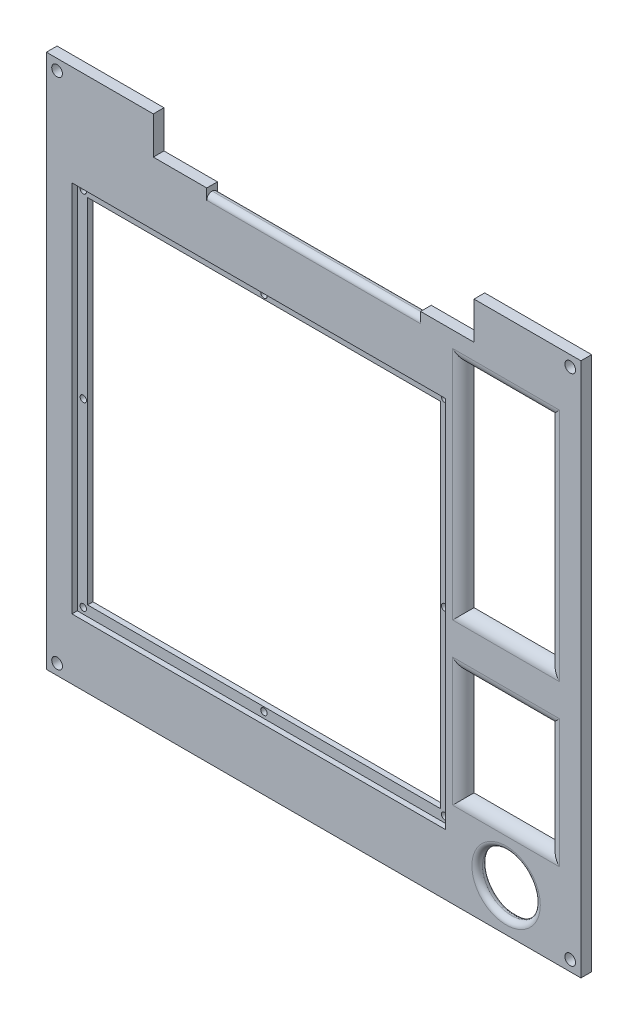
SolidWorks part; units mm, degrees
ref_plane "Ebene vorne" through (0, 0, 0) normal (0, 0, 1) x (1, 0, 0)
ref_plane "Ebene oben" through (0, 0, 0) normal (0, 1, 0) x (1, 0, 0)
ref_plane "Ebene rechts" through (0, 0, 0) normal (1, 0, 0) x (0, 0, -1)
sketch "Sketch1" plane through (0, 0, 0) normal (0, 0, 1) x (1, 0, 0)
  line L1 (0, 0) -> (-250, 0)
  line L2 (0, 0) -> (0, 250)
  line L3 (0, 250) -> (-250, 250)
  line L4 (-250, 0) -> (-250, 250)
  dimension "D1" = 250
  dimension "D2" = 250
extrude "Boss-Extrude1" add sketch "Sketch1" along normal blind 50
sketch "Sketch2" plane through (0, 0, 50) normal (0, 0, 1) x (1, 0, 0)
  line L0 (-125, 250) -> (-125, 0) construction
  line L1 (0, 250) -> (-250, 250) construction
  line L2 (-250, 0) -> (0, 0) construction
  line L5 (0, 0) -> (0, 250) construction
  line L7 (-55, 220) -> (-15, 220)
  line L8 (-55, 220) -> (-55, 120)
  line L9 (-55, 120) -> (-15, 120)
  line L10 (-15, 220) -> (-15, 120)
  line L14 (-55, 95) -> (-15, 95)
  line L15 (-55, 95) -> (-55, 45)
  line L16 (-55, 45) -> (-15, 45)
  line L17 (-15, 95) -> (-15, 45)
  dimension "D1" = 100
  dimension "D2" = 40
  dimension "D3" = 30
  dimension "D4" = 15
  dimension "D5" = 50
  dimension "D6" = 25
extrude "Cut-Extrude1" cut sketch "Sketch2" against normal blind 45
fillet "Fillet1" radius 5 4 edges at (-35, 120, 50) (-15, 170, 50) (-55, 170, 50) (-35, 220, 50)
fillet "Fillet2" radius 5 4 edges at (-35, 45, 50) (-15, 70, 50) (-35, 95, 50) (-55, 70, 50)
sketch "Sketch4" plane through (0, 0, 50) normal (0, 0, 1) x (1, 0, 0)
  line L0 (0, 250) -> (-250, 250) construction
  line L1 (-200, 250) -> (-175, 250)
  line L2 (-200, 250) -> (-200, 232.5)
  line L3 (-200, 232.5) -> (-175, 232.5)
  line L4 (-175, 250) -> (-175, 232.5)
  line L5 (-125, 250) -> (-125, 0) construction
  line L10 (-250, 0) -> (0, 0) construction
  line L11 (-50, 232.5) -> (-75, 232.5)
  line L12 (-75, 250) -> (-75, 232.5)
  line L13 (-50, 250) -> (-75, 250)
  line L14 (-50, 250) -> (-50, 232.5)
  dimension "D1" = 50
  dimension "D2" = 25
  dimension "D3" = 17.5
sketch "Sketch5" plane through (0, 0, 50) normal (0, 0, 1) x (1, 0, 0)
  line L0 (-235, 200) -> (-75, 200) construction
  line L1 (0, 250) -> (-250, 250) construction
  line L2 (-75, 200) -> (-75, 10) construction
  line L3 (-75, 10) -> (-235, 10) construction
  line L4 (-235, 10) -> (-235, 200) construction
  line L5 (-250, 250) -> (-250, 0) construction
  line L6 (-60, 115) -> (-60, 225) construction
  line L7 (-250, 0) -> (0, 0) construction
  line L9 (-235, 200) -> (-215, 200) construction
  line L10 (-235, 200) -> (-235, 180) construction
  line L11 (-235, 180) -> (-215, 180) construction
  line L12 (-215, 200) -> (-215, 180) construction
  line L13 (-235, 200) -> (-215, 180) construction
  line L14 (-235, 180) -> (-215, 200) construction
  circle A0 centre (-225, 190) radius 6.25
  dimension "D5" = 12.5
  dimension "D1" = 15
  dimension "D2" = 50
  dimension "D3" = 15
  dimension "D4" = 10
  dimension "D6" = 20
  dimension "D7" = 20
extrude "Cut-Extrude2" cut sketch "Sketch5" against normal blind 22
fillet "Fillet5" radius 1.5 1 edges at (-218.75, 190, 50)
pattern_linear "LPattern4" count 10 spacing 16.5 along (1, 0, 0) count 10 spacing 16.5 along (0, -1, 0) of "Cut-Extrude2", "Fillet5"
sketch "Sketch7" plane through (0, 0, 0) normal (0, 0, -1) x (-1, 0, 0)
  line L0 (250, 250) -> (250, 0) construction
  line L1 (5, 245) -> (245, 245)
  line L2 (5, 245) -> (5, 225)
  line L3 (5, 5) -> (245, 5)
  line L4 (245, 245) -> (245, 5)
  line L5 (0, 250) -> (250, 250) construction
  line L6 (0, 0) -> (0, 250) construction
  line L7 (250, 0) -> (0, 0) construction
  line L8 (5, 115) -> (5, 100)
  line L9 (5, 225) -> (60, 225)
  line L11 (5, 115) -> (60, 115)
  line L12 (60, 225) -> (60, 115)
  line L13 (5, 40) -> (60, 40)
  line L15 (5, 100) -> (60, 100)
  line L16 (60, 40) -> (60, 100)
  line L17 (5, 40) -> (5, 5)
  line L18 (60, 225) -> (10, 225) construction
  dimension "D1" = 5
  dimension "D2" = 5
  dimension "D3" = 5
  dimension "D4" = 5
extrude "Cut-Extrude4" cut sketch "Sketch7" against normal blind 45
sketch "Sketch8" plane through (0, 0, 50) normal (0, 0, 1) x (1, 0, 0)
  line L0 (0, 250) -> (-250, 250) construction
  line L1 (-175, 250) -> (-75, 250)
  line L2 (-175, 250) -> (-175, 230)
  line L3 (-175, 230) -> (-75, 230)
  line L4 (-75, 250) -> (-75, 230)
  point P6 (-125, 250)
  point P7 (-125, 250)
  dimension "D1" = 100
  dimension "D2" = 20
extrude "Cut-Extrude5" cut sketch "Sketch8" against normal blind 30
fillet "Fillet6" radius 2.5 2 edges at (-125, 230, 45) (-125, 230, 50)
fillet "Fillet7" radius 2 2 edges at (-125, 250, 20) (-125, 245, 20)
sketch "Sketch10" plane through (0, 0, 50) normal (0, 0, 1) x (1, 0, 0)
  line L2 (-35, 40) -> (-35, 0) construction
  line L3 (-10, 40) -> (-60, 40) construction
  line L4 (-250, 0) -> (0, 0) construction
  circle A0 centre (-35, 20) radius 13.5
  dimension "D1" = 27
extrude "Cut-Extrude6" cut sketch "Sketch10" against normal through all
extrude "Cut-Extrude7" cut sketch "Sketch4" against normal blind 10
sketch "Sketch12" plane through (0, 0, 45) normal (0, 0, -1) x (-1, 0, 0)
  line L0 (17.3, 19.25) -> (51.5, 19.25) construction
  line L1 (17.3, 32.5) -> (51.5, 32.5) construction
  line L2 (17.3, 32.5) -> (17.3, 6) construction
  line L3 (17.3, 6) -> (51.5, 6) construction
  line L4 (51.5, 32.5) -> (51.5, 6) construction
  line L5 (35, 40) -> (35, 0) construction
  line L6 (17.3, 20) -> (51.5, 20) construction
  circle A0 centre (46.4, 29.3) radius 2.5
  circle A2 centre (20.1, 29.3) radius 2.5
  circle A3 centre (20.1, 29.3) radius 1.5
  circle A4 centre (46.4, 29.3) radius 1.5
  circle A5 centre (20.1, 9.2) radius 1.5
  circle A6 centre (20.1, 9.2) radius 2.5
  circle A7 centre (46.4, 9.2) radius 1.5
  circle A8 centre (46.4, 9.2) radius 2.5
  dimension "D3" = 5
  dimension "D4" = 2.8
  dimension "D5" = 3.2
  dimension "D6" = 5
  dimension "D7" = 5.1
  dimension "D9" = 3
  dimension "D10" = 3
  dimension "D1" = 34.2
  dimension "D2" = 26.5
  dimension "D8" = 3.2
  dimension "D11" = 16.5
  dimension "D12" = 13.25
  dimension "D13" = 14
fillet "Verrundung1" radius 2.5 2 edges at (-48.5, 20, 45) (-21.5, 20, 50)
sketch "Skizze2" plane through (0, 245, 0) normal (0, -1, 0) x (1, 0, 0)
  line L0 (-175, 18) -> (-175, 40) construction
  line L1 (-175, 40) -> (-200, 40)
  line L2 (-175, 40) -> (-175, 35)
  line L3 (-175, 35) -> (-200, 35)
  line L4 (-200, 40) -> (-200, 35)
  line L5 (-200, 40) -> (-175, 40) construction
  line L6 (-125, 50) -> (-125, 0) construction
  line L7 (-250, 50) -> (0, 50) construction
  line L8 (-250, 0) -> (0, 0) construction
  line L9 (-50, 40) -> (-50, 35)
  line L10 (-75, 35) -> (-50, 35)
  line L11 (-75, 40) -> (-75, 35)
  line L12 (-75, 40) -> (-50, 40)
  dimension "D1" = 25
  dimension "D2" = 5
extrude "Aufsatz-Linear austragen1" add sketch "Skizze2" along normal blind 12.5
sketch "Skizze4" plane through (0, 0, 45) normal (0, 0, -1) x (-1, 0, 0)
  line L0 (75, 232.5) -> (75, 227.5) construction
  line L1 (50, 232.5) -> (75, 232.5)
  line L3 (49, 227.5) -> (75, 227.5)
  line L4 (75, 232.5) -> (75, 227.5)
  line L5 (175, 227.5) -> (175, 232.5) construction
  line L6 (200, 232.5) -> (175, 232.5)
  line L8 (201, 227.5) -> (175, 227.5)
  line L9 (175, 232.5) -> (175, 227.5)
  line L10 (50, 245) -> (5, 245) construction
  line L12 (50, 232.5) -> (50, 245)
  line L13 (50, 245) -> (49, 245)
  line L14 (49, 227.5) -> (49, 245)
  line L15 (245, 245) -> (200, 245) construction
  line L17 (200, 232.5) -> (200, 245)
  line L18 (200, 245) -> (201, 245)
  line L19 (201, 227.5) -> (201, 245)
  dimension "D1" = 5
  dimension "D2" = 5
  dimension "D3" = 1
  dimension "D4" = 1
extrude "Aufsatz-Linear austragen2" add sketch "Skizze4" along normal blind 10
sketch "Skizze11" plane through (0, 0, 50) normal (0, 0, 1) x (1, 0, 0)
  line L1 (-232.75, 197.75) -> (-68.75, 197.75)
  line L2 (-232.75, 197.75) -> (-232.75, 33.75)
  line L3 (-232.75, 33.75) -> (-68.75, 33.75)
  line L4 (-68.75, 197.75) -> (-68.75, 33.75)
  circle A0 centre (-175.5, 190) radius 7.75 construction
  circle A1 centre (-225, 173.5) radius 7.75 construction
  circle A2 centre (-76.5, 157) radius 7.75 construction
  circle A3 centre (-159, 41.5) radius 7.75 construction
extrude "Schnitt-Linear austragen6" cut sketch "Skizze11" against normal blind 10
sketch "Skizze12" plane through (0, 0, 50) normal (0, 0, 1) x (1, 0, 0)
  line L18 (-237.75, 28.75) -> (-63.75, 28.75)
  line L19 (-63.75, 28.75) -> (-63.75, 202.75)
  line L20 (-237.75, 202.75) -> (-237.75, 28.75)
  line L21 (-63.75, 202.75) -> (-237.75, 202.75)
  line L22 (-237.75, 28.75) -> (-63.75, 28.75)
  line L23 (-63.75, 28.75) -> (-63.75, 202.75)
  line L24 (-237.75, 202.75) -> (-237.75, 28.75)
  line L25 (-63.75, 202.75) -> (-237.75, 202.75)
  dimension "D1" = 5
extrude "Schnitt-Linear austragen7" cut sketch "Skizze12" against normal blind 2.5
sketch "Skizze13" plane through (0, 0, 47.5) normal (0, 0, 1) x (1, 0, 0)
  line L0 (-232.75, 115.75) -> (-237.75, 115.75) construction
  line L1 (-232.75, 33.75) -> (-232.75, 197.75) construction
  line L2 (-237.75, 202.75) -> (-237.75, 28.75) construction
  line L3 (-150.75, 202.75) -> (-150.75, 197.75) construction
  line L4 (-63.75, 202.75) -> (-237.75, 202.75) construction
  line L5 (-232.75, 197.75) -> (-68.75, 197.75) construction
  line L6 (-68.75, 115.75) -> (-63.75, 115.75) construction
  line L7 (-68.75, 197.75) -> (-68.75, 33.75) construction
  line L8 (-63.75, 28.75) -> (-63.75, 202.75) construction
  line L9 (-150.75, 33.75) -> (-150.75, 28.75) construction
  line L10 (-68.75, 33.75) -> (-232.75, 33.75) construction
  line L11 (-237.75, 28.75) -> (-63.75, 28.75) construction
  circle A0 centre (-235.25, 200.25) radius 1.5
  circle A1 centre (-150.75, 200.25) radius 1.5
  circle A2 centre (-66.25, 200.25) radius 1.5
  circle A3 centre (-235.25, 115.75) radius 1.5
  circle A4 centre (-66.25, 115.75) radius 1.5
  circle A5 centre (-66.25, 31.25) radius 1.5
  circle A6 centre (-150.75, 31.25) radius 1.5
  circle A7 centre (-235.25, 31.25) radius 1.5
  point P27 (-235.25, 115.75)
  point P28 (-150.75, 200.25)
  point P33 (-66.25, 115.75)
  dimension "D1" = 3
  dimension "D2" = 3
  dimension "D3" = 3
  dimension "D4" = 3
  dimension "D5" = 3
extrude "Schnitt-Linear austragen8" cut sketch "Skizze13" against normal blind 2.5
sketch "Skizze14" plane through (0, 0, 45) normal (0, 0, -1) x (-1, 0, 0)
  line L1 (0, 250) -> (10, 250)
  line L2 (0, 250) -> (0, 240)
  line L3 (0, 240) -> (10, 240)
  line L4 (10, 250) -> (10, 240)
  line L5 (240, 240) -> (250, 240)
  line L6 (250, 250) -> (250, 240)
  line L7 (240, 250) -> (250, 250)
  line L8 (240, 250) -> (240, 240)
  line L9 (240, 0) -> (250, 0)
  line L10 (250, 10) -> (250, 0)
  line L11 (240, 10) -> (250, 10)
  line L12 (240, 10) -> (240, 0)
  line L13 (0, 0) -> (10, 0)
  line L14 (10, 10) -> (10, 0)
  line L15 (0, 10) -> (10, 10)
  line L16 (0, 10) -> (0, 0)
  line L17 (250, 250) -> (250, 0) construction
  line L18 (250, 0) -> (0, 0) construction
  dimension "D1" = 10
  dimension "D2" = 10
  dimension "D3" = 2
  dimension "D4" = 2
extrude "Aufsatz-Linear austragen3" add sketch "Skizze14" along direction (0, 0, 1) on the side of the normal up to surface (45 mm away) up to face at (-63.3333, 121.6667, 0)
sketch "Skizze16" plane through (-250, 0, 0) normal (-1, 0, 0) x (0, 0, 1)
  line L0 (50, 0) -> (0, 0) construction
  line L1 (0, 250) -> (45, 250)
  line L2 (0, 250) -> (0, 0)
  line L3 (0, 0) -> (45, 0)
  line L4 (45, 250) -> (45, 0)
  line L5 (50, 250) -> (50, 0) construction
  dimension "D1" = 5
extrude "Schnitt-Linear austragen9" cut sketch "Skizze16" against normal through all
sketch "Skizze17" plane through (0, 0, 50) normal (0, 0, 1) x (1, 0, 0)
  line L0 (-200, 250) -> (-250, 250) construction
  line L1 (0, 0) -> (0, 250) construction
  line L2 (-250, 250) -> (-250, 0) construction
  line L3 (-250, 0) -> (0, 0) construction
  circle A0 centre (-245, 245) radius 2.5
  circle A1 centre (-5, 245) radius 2.5
  circle A2 centre (-5, 5) radius 2.5
  circle A3 centre (-245, 5) radius 2.5
  dimension "D1" = 5
  dimension "D2" = 5
  dimension "D3" = 5
  dimension "D6" = 5
  dimension "D7" = 5
  dimension "D8" = 5
  dimension "D4" = 2
  dimension "D5" = 2
extrude "Schnitt-Linear austragen10" cut sketch "Skizze17" against normal blind 5
sketch "Skizze18" plane through (0, 0, 50) normal (0, 0, 1) x (1, 0, 0)
  line L14 (-63.45, 203.05) -> (-238.05, 203.05)
  line L15 (-63.45, 28.45) -> (-63.45, 203.05)
  line L16 (-238.05, 28.45) -> (-63.45, 28.45)
  line L17 (-238.05, 203.05) -> (-238.05, 28.45)
  line L18 (-63.45, 203.05) -> (-238.05, 203.05)
  line L19 (-63.45, 28.45) -> (-63.45, 203.05)
  line L20 (-238.05, 28.45) -> (-63.45, 28.45)
  line L21 (-238.05, 203.05) -> (-238.05, 28.45)
  dimension "D1" = 0.3
extrude "Schnitt-Linear austragen11" cut sketch "Skizze18" against normal blind 2.5
sketch "Skizze19" plane through (0, 0, 47.5) normal (0, 0, 1) x (1, 0, 0)
  line L14 (-68.25, 33.25) -> (-68.25, 198.25)
  line L15 (-233.25, 33.25) -> (-68.25, 33.25)
  line L16 (-233.25, 198.25) -> (-233.25, 33.25)
  line L17 (-68.25, 198.25) -> (-233.25, 198.25)
  line L18 (-68.25, 33.25) -> (-68.25, 198.25)
  line L19 (-233.25, 33.25) -> (-68.25, 33.25)
  line L20 (-233.25, 198.25) -> (-233.25, 33.25)
  line L21 (-68.25, 198.25) -> (-233.25, 198.25)
  dimension "D1" = 0.5
extrude "Schnitt-Linear austragen12" cut sketch "Skizze19" against normal blind 2.5
